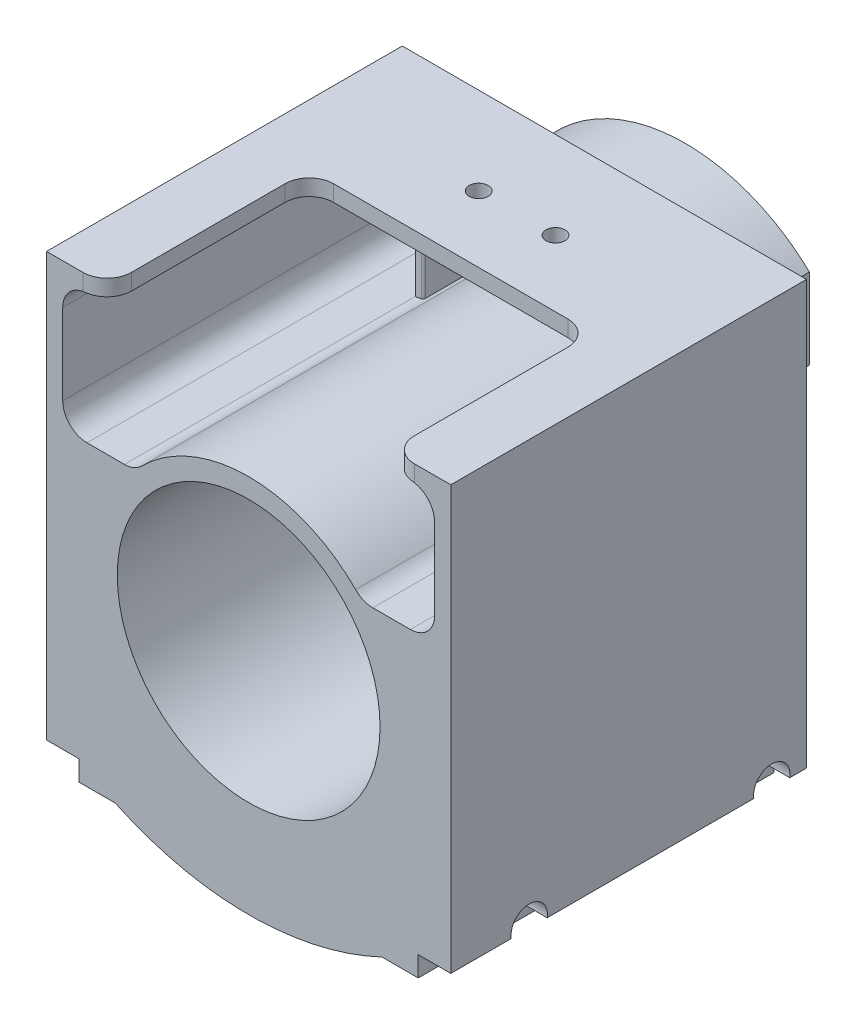
SolidWorks part; units mm, degrees
ref_plane "Front Plane" through (0, 0, 0) normal (0, 0, 1) x (1, 0, 0)
ref_plane "Top Plane" through (0, 0, 0) normal (0, 1, 0) x (1, 0, 0)
ref_plane "Right Plane" through (0, 0, 0) normal (1, 0, 0) x (0, 0, -1)
sketch "Sketch1" plane through (0, 0, 0) normal (0, 0, 1) x (1, 0, 0)
  line L1 (0, 0) -> (0, -38.55) construction
  line L2 (-25, 0) -> (-25, -29.3445)
  line L3 (25, 0) -> (25, -29.3445)
  line L4 (-25, 0) -> (-25, 20)
  line L5 (-25, 20) -> (25, 20)
  line L6 (25, 20) -> (25, 0)
  line L7 (25, -29.3445) -> (25, -32.3445)
  line L8 (25, -32.3445) -> (20.9746, -32.3445)
  line L9 (20.9746, -32.3445) -> (20.9746, -34.8445)
  line L10 (20.9746, -34.8445) -> (16.4912, -34.8445)
  line L11 (-20.9746, -34.8445) -> (-16.4912, -34.8445)
  line L12 (-20.9746, -32.3445) -> (-20.9746, -34.8445)
  line L13 (-25, -32.3445) -> (-20.9746, -32.3445)
  line L14 (-25, -29.3445) -> (-25, -32.3445)
  arc A0 (-25, -29.3445) -> (-20.9746, -32.3445) centre (0, 0) ccw construction
  arc A1 (20.9746, -32.3445) -> (25, -29.3445) centre (0, 0) ccw construction
  arc A2 (16.4912, -34.8445) -> (20.9746, -32.3445) centre (0, 0) ccw construction
  arc A3 (-16.4912, -34.8445) -> (16.4912, -34.8445) centre (0, 0) ccw
  arc A4 (-20.9746, -32.3445) -> (-16.4912, -34.8445) centre (0, 0) ccw construction
  dimension "D1" = 77.1
  dimension "D2" = 50
  dimension "D3" = 20
  dimension "D4" = 3
  dimension "D5" = 2.5
extrude "Boss-Extrude2" add sketch "Sketch1" along normal blind 44 from offset 6
sketch "Sketch2" plane through (0, 0, 50) normal (0, 0, 1) x (1, 0, 0)
  line L6 (0, 5.95) -> (0, -26.55) construction
  circle A0 centre (0, -10.3) radius 16.25
  dimension "D2" = 32.5
  dimension "D1" = 10.3
extrude "Cut-Extrude1" cut sketch "Sketch2" against normal through all both
sketch "Sketch4" plane through (0, 0, 50) normal (0, 0, 1) x (1, 0, 0)
  line L0 (-23, 18) -> (23, 18)
  line L3 (0, 20) -> (0, 5.95) construction
  line L4 (25, 20) -> (-25, 20) construction
  line L5 (23, 2) -> (14.0609, 2)
  line L6 (-23, 18) -> (-23, 2)
  line L7 (-23, 2) -> (-14.0609, 2)
  line L8 (-25, 20) -> (-25, -32.3445) construction
  line L9 (23, 18) -> (23, 2)
  circle A2 centre (0, -10.3) radius 16.25 construction
  arc A3 (14.0609, 2) -> (-14.0609, 2) centre (0, -10.3) ccw
  point P2 (0, 12.975)
  point P14 (0, 18)
  dimension "D1" = 37.3631
  dimension "D2" = 2
  dimension "D3" = 2
  dimension "D4" = 16
extrude "Cut-Extrude3" cut sketch "Sketch4" against normal through all
fillet "Fillet1" radius 3 6 edges at (23, 18, 28) (23, 2, 28) (14.0609, 2, 28) (-14.0609, 2, 28) (-23, 2, 28) (-23, 18, 28)
sketch "Sketch5" plane through (0, 20, 0) normal (0, 1, 0) x (1, 0, 0)
  line L0 (25, -50) -> (-25, -50) construction
  line L1 (-17.5, -50) -> (17.5, -50)
  line L2 (-17.5, -50) -> (-17.5, -25)
  line L3 (-17.5, -25) -> (17.5, -25)
  line L4 (17.5, -50) -> (17.5, -25)
  line L5 (0, 0) -> (0, -50) construction
  dimension "D1" = 35
  dimension "D2" = 25
extrude "Cut-Extrude4" cut sketch "Sketch5" against normal blind 10
fillet "Fillet2" radius 3 4 edges at (17.5, 19, 50) (17.5, 19, 25) (-17.5, 19, 25) (-17.5, 19, 50)
ref_plane "Plane1" through (0, 0, 14) normal (0, 0, 1) x (1, 0, 0)
sketch "Sketch6" plane through (0, 0, 14) normal (0, 0, 1) x (1, 0, 0)
  line L0 (0, -10.3) -> (0, 2.7) construction
  line L1 (0, -10.3) -> (4.4463, 1.916) construction
  circle A1 centre (0, -10.3) radius 16.25 construction
  circle A3 centre (0, -10.3) radius 9.5
  circle A8 centre (0, -10.3) radius 16.25
  circle A9 centre (0, -10.3) radius 13 construction
  circle A10 centre (4.4463, 1.916) radius 1.65
  circle A11 centre (12.216, -14.7463) radius 1.65
  circle A12 centre (-4.4463, -22.516) radius 1.65
  circle A13 centre (-12.216, -5.8537) radius 1.65
  dimension "D1" = 19
  dimension "D6" = 13
  dimension "D2" = 3.5
  dimension "D3" = 3.3
  dimension "D4" = 20
  dimension "D5" = 4
extrude "Boss-Extrude3" add sketch "Sketch6" against normal blind 5
sketch "Sketch7" plane through (0, 0, 0) normal (1, 0, 0) x (0, 0, -1)
  circle A0 centre (-40.3, -32) radius 2.25
  circle A1 centre (-10.3, -32) radius 2.25
  dimension "D3" = 4.5
  dimension "D1" = 32
  dimension "D2" = 10.3
  dimension "D4" = 30
extrude "Cut-Extrude5" cut sketch "Sketch7" against normal through all both and the other way through all
sketch "Sketch8" plane through (0, 20, 0) normal (0, 1, 0) x (1, 0, 0)
  line L0 (0, -6) -> (0, -25) construction
  line L1 (25, -6) -> (-25, -6) construction
  line L2 (14.5, -25) -> (-14.5, -25) construction
  circle A0 centre (-4.75, -16.8) radius 1.175
  circle A1 centre (4.75, -16.8) radius 1.175
  dimension "D1" = 2.35
  dimension "D2" = 9.5
  dimension "D3" = 10.8
extrude "Cut-Extrude6" cut sketch "Sketch8" against normal up to next contours A0 | A1
sketch "Sketch9" plane through (0, 0, 50) normal (0, 0, 1) x (1, 0, 0)
  line L0 (0, -28.8) -> (0, -5.3) construction
  line L1 (0, -10.3) -> (0, -28.8) construction
  line L2 (-15.3623, 2) -> (-15.3623, 10.9768)
  line L3 (15.3623, 2) -> (15.3623, 10.9768)
  line L4 (0, 8.3815) -> (0, 17.0815) construction
  line L5 (-14.3623, 2.1716) -> (-14.3623, 10.0902)
  line L6 (14.3623, 2.1716) -> (14.3623, 10.0902)
  line L7 (-15.3623, 2) -> (-15.3623, 1)
  line L8 (15.3623, 2) -> (15.3623, 1)
  line L9 (14.3623, 2) -> (14.3623, 10.5397) construction
  line L10 (-14.3623, 2) -> (-14.3623, 10.5397) construction
  arc A0 (13.2366, 2.883) -> (-13.2366, 2.883) centre (0, -10.3) ccw construction
  arc A1 (13.2366, 2.883) -> (-13.2366, 2.883) centre (0, -10.3) ccw
  arc A3 (-15.3623, 10.9768) -> (15.3623, 10.9768) centre (0, -5.3) cw
  arc A4 (13.2366, 2.883) -> (15.3623, 2) centre (15.3623, 5) ccw construction
  arc A5 (-15.3623, 2) -> (-13.2366, 2.883) centre (-15.3623, 5) ccw construction
  arc A6 (13.2366, 2.883) -> (15.3623, 2) centre (15.3623, 5) ccw
  arc A7 (-15.3623, 2) -> (-13.2366, 2.883) centre (-15.3623, 5) ccw
  arc A8 (12.5281, 2.1773) -> (15.3623, 1) centre (15.3623, 5) ccw
  arc A9 (12.5281, 2.1773) -> (-12.5281, 2.1773) centre (0, -10.3) ccw
  arc A10 (-15.3623, 1) -> (-12.5281, 2.1773) centre (-15.3623, 5) ccw
  arc A11 (-14.0179, 10.8453) -> (14.0179, 10.8453) centre (0, -5.3) cw
  arc A12 (-14.3623, 10.5397) -> (14.3623, 10.5397) centre (0, -5.3) cw construction
  arc A13 (14.3623, 10.0902) -> (14.0179, 10.8453) centre (13.3623, 10.0902) ccw
  arc A14 (-14.3623, 10.0902) -> (-14.0179, 10.8453) centre (-13.3623, 10.0902) cw
  dimension "D1" = 8.7
  dimension "D2" = 1
  dimension "D4" = 1
  dimension "Ring Gear Outer Dia to Center" = 23.5
  dimension "Pinion to Ring Gear Outer Diameter" = 18.5
  dimension "D3" = 1
extrude "Boss-Extrude4" add sketch "Sketch9" along normal blind 8 and the other way blind 10 from surface contours L5 A11 L6 L2 L3 A3 A6 | L7 A10 A9 A8 L8 L2 L3 A6 region at (-14.8015, 1.7318, 50) region at (-15.02, 6.4884, 50) starting at face at (0, 7.9034, 6)
fillet "Fillet5" radius 0.25 8 edges at (13.7595, 2.464, -4) (-13.7595, 2.464, -4) (14.3623, 6.1309, -4) (14.2721, 10.5051, -4) (-14.3623, 6.1309, -4) (-14.2721, 10.5051, -4) (0, 8.3815, -4) (0, 16.0815, -4)
fillet "Fillet6" radius 0.25 5 edges at (14.3623, 6.1309, 14) (14.2721, 10.5051, 14) (-14.3623, 6.1309, 14) (-14.2721, 10.5051, 14) (0, 16.0815, 14)
